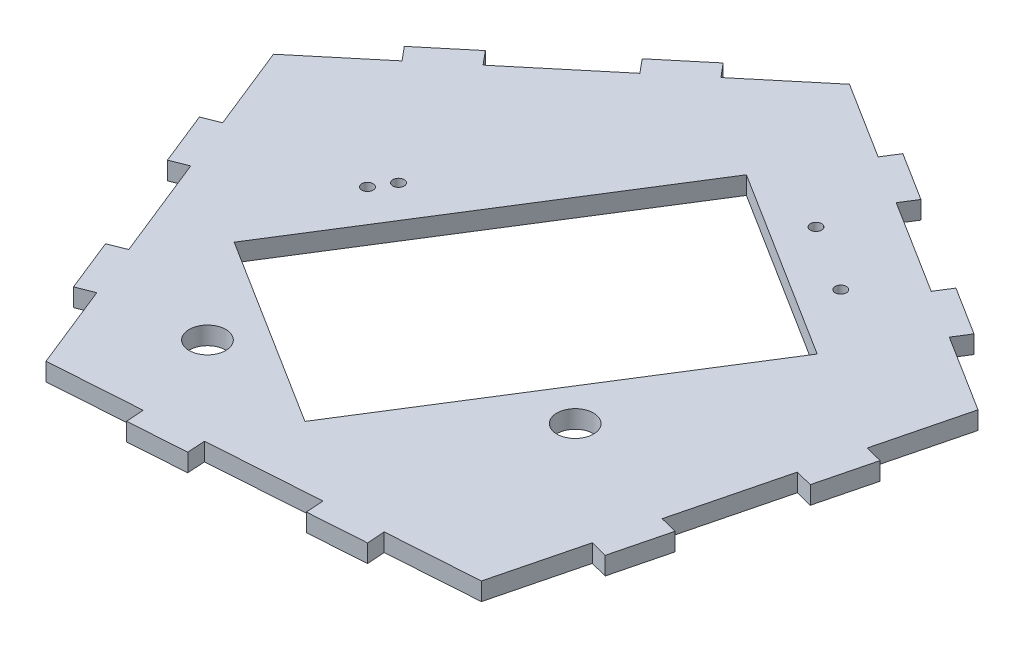
SolidWorks part; units mm, degrees
ref_plane "Front Plane" through (0, 0, 0) normal (0, 0, 1) x (1, 0, 0)
ref_plane "Top Plane" through (0, 0, 0) normal (0, 1, 0) x (1, 0, 0)
ref_plane "Right Plane" through (0, 0, 0) normal (1, 0, 0) x (0, 0, -1)
sketch "Sketch1" plane through (0, 0, 0) normal (0, 1, 0) x (1, 0, 0)
  line L1 (-59.9258, 15.1181) -> (-32.8962, -52.3211)
  line L2 (-32.8962, -52.3211) -> (39.5948, -47.4543)
  line L3 (39.5948, -47.4543) -> (57.3672, 22.9927)
  line L4 (57.3672, 22.9927) -> (-4.14, 61.6646)
  line L5 (-4.14, 61.6646) -> (-59.9258, 15.1181)
  circle A0 centre (0, 0) radius 50 construction
  dimension "D1" = 100
extrude "Boss-Extrude1" add sketch "Sketch1" along normal blind 3.18
ref_axis "Axis" through (0, 3.339, 0) along (0, -1, 0)
sketch "Axis Check" plane through (0, 3.18, 0) normal (0, 1, 0) x (1, 0, 0)
  line L0 (3.3493, -49.8877) -> (-4.14, 61.6646) construction
  line L1 (-32.8962, -52.3211) -> (39.5948, -47.4543) construction
  line L2 (57.3672, 22.9927) -> (-46.411, -18.6015) construction
  line L3 (-59.9258, 15.1181) -> (-32.8962, -52.3211) construction
  line L4 (-32.0329, 38.3913) -> (39.5948, -47.4543) construction
  line L5 (-4.14, 61.6646) -> (-59.9258, 15.1181) construction
  line L6 (-59.9258, 15.1181) -> (48.481, -12.2308) construction
  line L7 (39.5948, -47.4543) -> (57.3672, 22.9927) construction
  line L8 (-32.8962, -52.3211) -> (26.6136, 42.3287) construction
  line L9 (57.3672, 22.9927) -> (-4.14, 61.6646) construction
sketch "Sketch2" plane through (0, 0, 0) normal (0, -1, 0) x (1, 0, 0)
  line L0 (-53.8107, 0.1392) -> (-50.859, -1.0438)
  line L1 (-53.8107, 0.1392) -> (-50.1723, 9.2172)
  line L2 (-50.859, -1.0438) -> (-47.2205, 8.0342)
  line L3 (-50.1723, 9.2172) -> (-47.2205, 8.0342)
  line L4 (-59.9258, -15.1181) -> (-32.8962, 52.3211) construction
  line L5 (-42.6498, 27.9858) -> (-39.0113, 37.0638)
  line L6 (-42.6498, 27.9858) -> (-39.6981, 26.8028)
  line L7 (-39.0113, 37.0638) -> (-36.0596, 35.8808)
  line L8 (-39.6981, 26.8028) -> (-36.0596, 35.8808)
  line L9 (-46.411, 18.6015) -> (-19.2439, 7.7129) construction
  line L10 (-40.8306, 32.5248) -> (-37.8788, 31.3418) construction
  dimension "D1" = 3.18
  dimension "D2" = 9.78
  dimension "D3" = 10.11
extrude "Cut F" [suppressed] cut sketch "Sketch2" against normal through all
sketch "Sketch4" plane through (0, 3.18, 0) normal (0, 1, 0) x (1, 0, 0)
  line L9 (26.6136, 42.3287) -> (-26.6136, -42.3287) construction
  line L10 (57.3672, 22.9927) -> (-4.14, 61.6646) construction
  line L11 (-34.4964, -17.2915) -> (0.6335, 38.5824)
  line L12 (-34.4964, -17.2915) -> (-0.6335, -38.5824)
  line L13 (0.6335, 38.5824) -> (34.4964, 17.2915)
  line L14 (-0.6335, -38.5824) -> (34.4964, 17.2915)
  line L15 (-34.4964, -17.2915) -> (34.4964, 17.2915) construction
  line L16 (0.6335, 38.5824) -> (-0.6335, -38.5824) construction
  line L20 (0, 0) -> (39.0006, -24.5211) construction
  circle A0 centre (-21.8232, -34.7095) radius 3.25
  circle A1 centre (23.7041, -14.9036) radius 3.25
  point P5 (0, 0)
  point P6 (-21.8232, -34.7095)
  dimension "D3" = 6.5
  dimension "D1" = 40
  dimension "D2" = 66
  dimension "D4" = 8
  dimension "D5" = 8
extrude "Top Cut" cut sketch "Sketch4" against normal blind 10
sketch "Sketch7" plane through (0, 3.18, 0) normal (0, 1, 0) x (1, 0, 0)
  line L0 (0, 0) -> (26.6136, 42.3287) construction
  line L1 (57.3672, 22.9927) -> (-4.14, 61.6646) construction
  line L2 (-5.3227, -8.4657) -> (-29.0268, 6.4379) construction
  line L3 (-12.4958, -8.6807) -> (-31.1559, 3.0516) construction
  line L5 (0.6335, 38.5824) -> (-34.4964, -17.2915) construction
  circle A0 centre (-29.0268, 6.4379) radius 1
  circle A1 centre (-31.1559, 3.0516) radius 1
  dimension "D5" = 2
  dimension "D1" = 4
  dimension "D2" = 14
  dimension "D3" = 8
  dimension "D4" = 8
extrude "Top Cut 2" cut sketch "Sketch7" against normal through all
sketch "Sketch10" plane through (0, 3.18, 0) normal (0, 1, 0) x (1, 0, 0)
  line L0 (26.6136, 42.3287) -> (17.565, 27.9369) construction
  line L1 (57.3672, 22.9927) -> (-4.14, 61.6646) construction
  line L2 (34.4964, 17.2915) -> (0.6335, 38.5824) construction
  line L3 (30.1304, 27.124) -> (10.6872, 39.3486) construction
  circle A0 centre (14.8326, 36.7423) radius 1
  circle A1 centre (26.6846, 29.2905) radius 1
  dimension "D1" = 6
  dimension "D2" = 2
  dimension "D3" = 7
extrude "Top Cut 3" cut sketch "Sketch10" against normal blind 10
sketch "Sketch8" [suppressed] plane through (0, 3.18, 0) normal (0, 1, 0) x (1, 0, 0)
  line L0 (3.3493, -49.8877) -> (-4.14, 61.6646) construction
  line L5 (-32.8962, -52.3211) -> (39.5948, -47.4543) construction
  line L6 (-17.9455, -31.2723) -> (21.9647, -28.5929)
  line L11 (-17.9455, -31.2723) -> (-21.9647, 28.5929)
  line L12 (21.9647, -28.5929) -> (17.9455, 31.2723)
  line L13 (-21.9647, 28.5929) -> (17.9455, 31.2723)
  point P4 (1.4955, -22.2759)
  dimension "D1" = 60
  dimension "D2" = 40
  dimension "D3" = 20
extrude "Bottom Cut" [suppressed] cut sketch "Sketch8" against normal blind 10
sketch "Sketch9" [suppressed] plane through (0, 3.18, 0) normal (0, 1, 0) x (1, 0, 0)
  line L0 (19.9551, 1.3397) -> (-19.9551, -1.3397) construction
  line L1 (21.9647, -28.5929) -> (17.9455, 31.2723) construction
  line L2 (-21.9647, 28.5929) -> (-17.9455, -31.2723) construction
  line L3 (-19.9551, -1.3397) -> (-44.4689, -2.9855) construction
  line L4 (19.9551, 1.3397) -> (42.6839, 2.8657) construction
  line L5 (-32.8962, -52.3211) -> (39.5948, -47.4543) construction
  line L6 (-29.6051, -6.8886) -> (-32.3788, -7.0748)
  line L7 (-29.6051, -6.8886) -> (-30.2602, 2.8694)
  line L8 (-30.2602, 2.8694) -> (-33.0339, 2.6832)
  line L9 (-32.3788, -7.0748) -> (-33.0339, 2.6832)
  line L10 (-29.6051, -6.8886) -> (-33.0339, 2.6832) construction
  line L11 (-30.2602, 2.8694) -> (-32.3788, -7.0748) construction
  line L12 (33.0339, -2.6832) -> (30.2602, -2.8694)
  line L13 (33.0339, -2.6832) -> (32.3788, 7.0748)
  line L14 (32.3788, 7.0748) -> (29.6051, 6.8886)
  line L15 (30.2602, -2.8694) -> (29.6051, 6.8886)
  line L16 (33.0339, -2.6832) -> (29.6051, 6.8886) construction
  line L17 (32.3788, 7.0748) -> (30.2602, -2.8694) construction
  line L18 (-32.8962, -52.3211) -> (39.5948, -47.4543) construction
  point P6 (-31.3195, -2.1027)
  point P13 (31.3195, 2.1027)
  dimension "D1" = 9.78
  dimension "D4" = 9.78
  dimension "D5" = 10
  dimension "D6" = 10
  dimension "D2" = 2.78
  dimension "D3" = 2.78
extrude "Battery Holder Cut" [suppressed] cut sketch "Sketch9" against normal blind 3.18
sketch "Sketch3" plane through (0, 3.18, 0) normal (0, 1, 0) x (1, 0, 0)
  line L0 (0, 0) -> (-40.9819, 49.1167) construction
  line L1 (-49.5112, 27.9494) -> (-45.4366, 23.066)
  line L3 (-45.4366, 23.066) -> (-37.5894, 29.6135)
  line L4 (-41.664, 34.4969) -> (-37.5894, 29.6135)
  line L5 (-4.14, 61.6646) -> (-59.9258, 15.1181) construction
  line L6 (-71.9961, 5.0469) -> (-69.9588, 2.6052)
  line L7 (-71.9961, 5.0469) -> (-47.4739, 25.5077)
  line L14 (-26.4764, 47.1691) -> (-22.4018, 42.2857)
  line L16 (-22.4018, 42.2857) -> (-14.5546, 48.8333)
  line L17 (-18.6292, 53.7166) -> (-14.5546, 48.8333)
  line L18 (-42.539, 27.5695) -> (-41.513, 26.3398) construction
  line L19 (-49.5112, 27.9494) -> (-41.664, 34.4969)
  line L21 (-26.4764, 47.1691) -> (-18.6292, 53.7166)
  line L22 (-16.5919, 51.275) -> (4.7866, 69.1127)
  line L23 (-39.6267, 32.0552) -> (-24.4391, 44.7274)
  line M18 (-4.14, 61.6646) -> (-59.9258, 15.1181)
  dimension "D1" = 3.18
  dimension "D2" = 10.22
  dimension "D3" = 9.89
  dimension "D4" = 100
extrude "Extrude M" add sketch "Sketch3" against normal up to surface (3.18 mm away) contours L21 L14 L7 L17 | L19 L1 L4 M18 region at (-44.5689, 3.18, -30.0023) region at (-21.5341, 3.18, -49.222) up to face at (14.8326, 0, -35.7423)
pattern_circular "Circle F" [suppressed] count 5 over 360 about axis through (0, 3.339, 0) along (0, -1, 0) of bodies 173
pattern_circular "Circle M" count 5 over 360 about axis through (0, 3.339, 0) along (0, -1, 0) of "Extrude M"
pattern_circular "Circle Side F" [suppressed] count 5 over 360 about axis through (0, 3.339, 0) along (0, -1, 0) of bodies 173
pattern_circular "Circle Side M" [suppressed] count 5 over 360 about axis through (0, 3.339, 0) along (0, -1, 0) of bodies 168
equation "\"kerf\"= .22mm"
equation "\"tabWidthF\"= 10 - \"kerf\""
equation "\"tabThickness\"= 3.18"
equation "\"D1@Sketch2\"=\"tabThickness\""
equation "\"tabWidthM\"= 10 + \"kerf\""
equation "\"halfkerf\"= \"kerf\" / 2.00mm"
equation "\"D1@Sketch9\"=\"tabWidthF\""
equation "\"D4@Sketch9\"=\"tabWidthF\""
equation "\"D1@Battery Holder Cut\" = \"tabThickness\""
equation "\"tabLength\" = \"kerf\" + 12"
